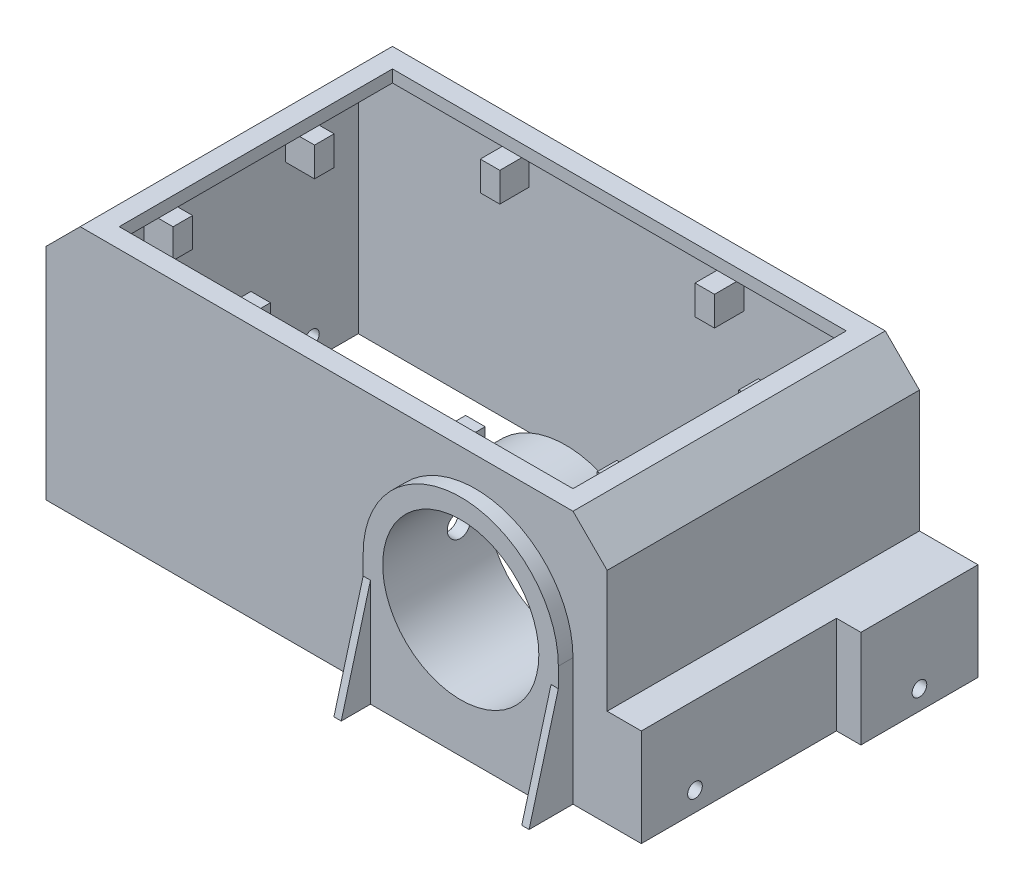
SolidWorks part; units mm, degrees
ref_plane "Alzado" through (0, 0, 0) normal (0, 0, 1) x (1, 0, 0)
ref_plane "Planta" through (0, 0, 0) normal (0, 1, 0) x (1, 0, 0)
ref_plane "Vista lateral" through (0, 0, 0) normal (1, 0, 0) x (0, 0, -1)
sketch "Croquis1" plane through (0, 0, 0) normal (0, 1, 0) x (1, 0, 0)
  line L1 (-63.5, -32) -> (63.5, -32)
  line L2 (-63.5, -32) -> (-63.5, 32)
  line L3 (-63.5, 32) -> (63.5, 32)
  line L4 (63.5, -32) -> (63.5, 32)
  line L5 (-63.5, -32) -> (63.5, 32) construction
  line L6 (-63.5, 32) -> (63.5, -32) construction
  point P0 (0, 0)
  dimension "D1" = 127
  dimension "D2" = 64
extrude "Saliente-Extruir1" add sketch "Croquis1" along normal blind 52
sketch "Croquis2" plane through (0, 0, 32) normal (0, 0, 1) x (1, 0, 0)
  line L0 (-63.5, 45) -> (-56.5003, 51.9997)
  line L1 (-63.5, 52) -> (-63.5, 0) construction
  line L2 (-56.5003, 51.9997) -> (-63.5, 52)
  line L3 (-63.5, 52) -> (-63.5, 45)
  line L4 (63.5, 0) -> (63.5, 20)
  line L5 (63.5, 52) -> (63.5, 0) construction
  line L6 (63.5, 20) -> (51.5, 20)
  line L7 (44.5003, 51.9997) -> (51.5, 45)
  line L8 (51.5, 45) -> (51.5, 20)
  line L9 (44.5003, 51.9997) -> (63.5, 52)
  line L10 (63.5, 52) -> (63.5, 20)
  line M9 (63.5, 0) -> (63.5, 52)
  line M11 (-63.5, 52) -> (-63.5, 0)
  dimension "D1" = 9.899
  dimension "D2" = 135
  dimension "D3" = 45
  dimension "D4" = 20
  dimension "D5" = 12
  dimension "D6" = 9.899
  dimension "D7" = 25
extrude "Cortar-Extruir1" cut sketch "Croquis2" against normal through all contours L0 L2 M11 | L9 L7 L8 L6 M9 region at (-61.1668, 49.6666, 32) region at (57.0003, 36.8195, 32)
sketch "Croquis3" plane through (0, 0, 32) normal (0, 0, 1) x (1, 0, 0)
  line L0 (-56.5003, 51.9997) -> (-56.4876, 52.4201)
  line L1 (-56.4876, 52.4201) -> (-63.8632, 52.6439)
  line L2 (-63.8632, 52.6439) -> (-63.8632, 51.3967)
  line L3 (-63.8632, 51.3967) -> (-58.4019, 51.7775)
  line L4 (-58.4019, 51.7775) -> (-56.5003, 51.9997)
  line L5 (44.5003, 51.9997) -> (64.7548, 55.7043)
  line L6 (64.7548, 55.7043) -> (64.7548, 48.4998)
  line L7 (64.7548, 48.4998) -> (44.5003, 51.9997)
extrude "Cortar-Extruir2" cut sketch "Croquis3" against normal through all
sketch "Croquis4" plane through (0, 0, 32) normal (0, 0, 1) x (1, 0, 0)
  line L0 (63.5, 0) -> (58.5, 0)
  line L1 (-63.5, 0) -> (63.5, 0) construction
  line L2 (58.5, 0) -> (58.5, 20)
  line L3 (63.5, 20) -> (51.5, 20) construction
  line L4 (58.5, 20) -> (63.5, 20)
  line L5 (63.5, 20) -> (63.5, 0)
  dimension "D1" = 5
extrude "Cortar-Extruir3" cut sketch "Croquis4" against normal blind 40
sketch "Croquis5" plane through (0, 0, 0) normal (0, -1, 0) x (1, 0, 0)
  line L0 (58.5, 32) -> (44.5, 32)
  line L1 (-63.5, 32) -> (58.5, 32) construction
  line L2 (44.5, 32) -> (44.5, 41)
  line L3 (44.5, 41) -> (43, 41)
  line L4 (43, 41) -> (43, 35)
  line L5 (43, 35) -> (6, 35)
  line L6 (6, 35) -> (6, 41)
  line L7 (6, 41) -> (4.5, 41)
  line L8 (4.5, 41) -> (4.5, 32)
  line L9 (4.5, 32) -> (44.5, 32)
  dimension "D1" = 14
  dimension "D2" = 9
  dimension "D3" = 1.5
  dimension "D4" = 6
  dimension "D5" = 37
  dimension "D6" = 1.5
extrude "Saliente-Extruir2" add sketch "Croquis5" against normal blind 26 contours L2 L3 L4 L5 L6 L7 L8 L9
shell "Vaciado1" thickness 2.5 removed face at (22.3571, 0, 20.1429)
sketch "Croquis6" plane through (44.5, 0, 0) normal (1, 0, 0) x (0, 0, -1)
  line L0 (-35, 22) -> (-41, 0)
  line L1 (-35, 26) -> (-41, 26)
  line L2 (-41, 26) -> (-41, 0)
  line L3 (-32, 26) -> (-32, 22)
  line L4 (-32, 26) -> (-32, 0) construction
  line L5 (-32, 26) -> (-35, 26)
  line L6 (-32, 26) -> (-41, 26) construction
  line L7 (-35, 26) -> (-35, 22)
  line L8 (-32, 0) -> (-41, 0) construction
  line M8 (-32, 26) -> (-41, 26)
  line M9 (-41, 26) -> (-41, 0)
  dimension "D1" = 74.745
  dimension "D2" = 4
  dimension "D3" = 3
extrude "Cortar-Extruir4" cut sketch "Croquis6" against normal through all contours L7 L0 M8 M9 region at (44.5, 17.1556, 38.7333)
sketch "Croquis7" plane through (0, 0, 32) normal (0, 0, 1) x (1, 0, 0)
  line L0 (44.5, 26) -> (4.5, 26) construction
  line L1 (4.5, 26) -> (44.5, 26)
  arc A0 (44.5, 26) -> (4.5, 26) centre (24.5, 26) ccw
extrude "Saliente-Extruir3" add sketch "Croquis7" along normal blind 3
sketch "Croquis8" plane through (0, 0, 35) normal (0, 0, 1) x (1, 0, 0)
  circle A0 centre (24.5, 26) radius 16
  dimension "D1" = 32
extrude "Cortar-Extruir5" cut sketch "Croquis8" against normal blind 10
sketch "Croquis9" plane through (0, 0, 32.5) normal (0, 0, -1) x (-1, 0, 0)
  circle A0 centre (-24.5, 26) radius 16
  circle A1 centre (-24.5, 26) radius 18.5
  dimension "D1" = 37
extrude "Saliente-Extruir4" add sketch "Croquis9" along normal blind 19
ref_plane "Plano1" through (6, 0, 0) normal (1, 0, 0) x (0, 0, -1)
sketch "Croquis11" plane through (6, 0, 0) normal (1, 0, 0) x (0, 0, -1)
  line L0 (-19.3603, 25.4085) -> (-29.5, 0)
  circle A0 centre (-19.3603, 25.4085) radius 2.42
  dimension "D2" = 4.84
  dimension "D1" = 27.357
extrude "Cortar-Extruir6" cut sketch "Croquis11" along normal blind 39 contours A0 region at (6, 23.4618, 18.0412)
sketch "Croquis12" plane through (0, 52, 0) normal (0, 1, 0) x (1, 0, 0)
  line L0 (-5.999, 32) -> (-5.999, -32) construction
  line L5 (-56.5003, 32) -> (-56.5003, -32) construction
  line L6 (-52.5003, -28) -> (40.5023, -28)
  line L7 (44.5023, 32) -> (-56.5003, 32) construction
  line L8 (-56.5003, -32) -> (44.5023, -32) construction
  line L9 (-52.5003, -28) -> (-52.5003, 28)
  line L10 (-52.5003, 28) -> (40.5023, 28)
  line L11 (40.5023, -28) -> (40.5023, 28)
  line L12 (-52.5003, -28) -> (40.5023, 28) construction
  line L13 (-52.5003, 28) -> (40.5023, -28) construction
  point P0 (-7.7164, 0)
  point P1 (-5.999, 0)
  dimension "D1" = 4
  dimension "D2" = 4
extrude "Cortar-Extruir8" cut sketch "Croquis12" against normal blind 5
sketch "Croquis13" plane through (0, 49.5, 0) normal (0, -1, 0) x (1, 0, 0)
  line L0 (-61, 29.5) -> (7, 29.5) construction
  line L1 (-29.9995, 29.5) -> (-25.9995, 29.5)
  line L2 (-29.9995, 29.5) -> (-29.9995, 23.5)
  line L3 (-29.9995, 23.5) -> (-25.9995, 23.5)
  line L4 (-25.9995, 29.5) -> (-25.9995, 23.5)
  line L5 (14.0005, 29.5) -> (18.0005, 29.5)
  line L6 (14.0005, 29.5) -> (14.0005, 23.5)
  line L7 (18.0005, 29.5) -> (18.0005, 23.5)
  line L8 (14.0005, 23.5) -> (18.0005, 23.5)
  line L9 (14.0005, -23.5) -> (18.0005, -23.5)
  line L10 (14.0005, -23.5) -> (14.0005, -29.5)
  line L11 (18.0005, -23.5) -> (18.0005, -29.5)
  line L12 (14.0005, -29.5) -> (18.0005, -29.5)
  line L13 (-29.9995, -23.5) -> (-25.9995, -23.5)
  line L14 (-29.9995, -23.5) -> (-29.9995, -29.5)
  line L15 (-25.9995, -23.5) -> (-25.9995, -29.5)
  line L16 (-29.9995, -29.5) -> (-25.9995, -29.5)
  line L17 (43.4645, -29.5) -> (-55.4645, -29.5) construction
  line L18 (-55.4645, 29.5) -> (-55.4645, 20) construction
  line L19 (-55.4645, 29.5) -> (-55.4645, -29.5) construction
  line L20 (-55.4645, 20) -> (-49.4645, 20)
  line L21 (-49.4645, 20) -> (-49.4645, 16)
  line L22 (-49.4645, 16) -> (-55.4645, 16)
  line L23 (-55.4645, 16) -> (-55.4645, 20)
  line L24 (37.4645, 20) -> (43.4645, 20)
  line L25 (43.4645, 16) -> (37.4645, 16)
  line L26 (37.4645, 16) -> (37.4645, 20)
  line L27 (43.4645, 20) -> (43.4645, 16)
  line L28 (37.4645, -9) -> (43.4645, -9)
  line L29 (43.4645, -13) -> (37.4645, -13)
  line L30 (37.4645, -13) -> (37.4645, -9)
  line L31 (43.4645, -9) -> (43.4645, -13)
  line L32 (-55.4645, -9) -> (-49.4645, -9)
  line L33 (-49.4645, -13) -> (-55.4645, -13)
  line L34 (-55.4645, -13) -> (-55.4645, -9)
  line L35 (-49.4645, -9) -> (-49.4645, -13)
  line L36 (43.4645, -29.5) -> (43.4645, 29.5) construction
  dimension "D1" = 25.465
  dimension "D2" = 6
  dimension "D3" = 4
  dimension "D6" = 0
  dimension "D7" = 40
  dimension "D8" = 40
  dimension "D9" = 9.5
  dimension "D10" = 6
  dimension "D11" = 4
  dimension "D14" = 0
  dimension "D15" = 25
  dimension "D4" = 2
  dimension "D5" = 2
  dimension "D12" = 2
  dimension "D13" = 2
extrude "Saliente-Extruir5" add sketch "Croquis13" along normal blind 6
sketch "Croquis14" plane through (-63.5, 0, 0) normal (-1, 0, 0) x (0, 0, 1)
  line L0 (-32, 45) -> (-32, 0) construction
  line L1 (-32, 0) -> (32, 0) construction
  circle A0 centre (-20, 4) radius 1.5
  circle A1 centre (21, 4) radius 1.5
  dimension "D2" = 3
  dimension "D3" = 4
  dimension "D5" = 3
  dimension "D1" = 12
  dimension "D4" = 41
extrude "Cortar-Extruir9" cut sketch "Croquis14" against normal through all
